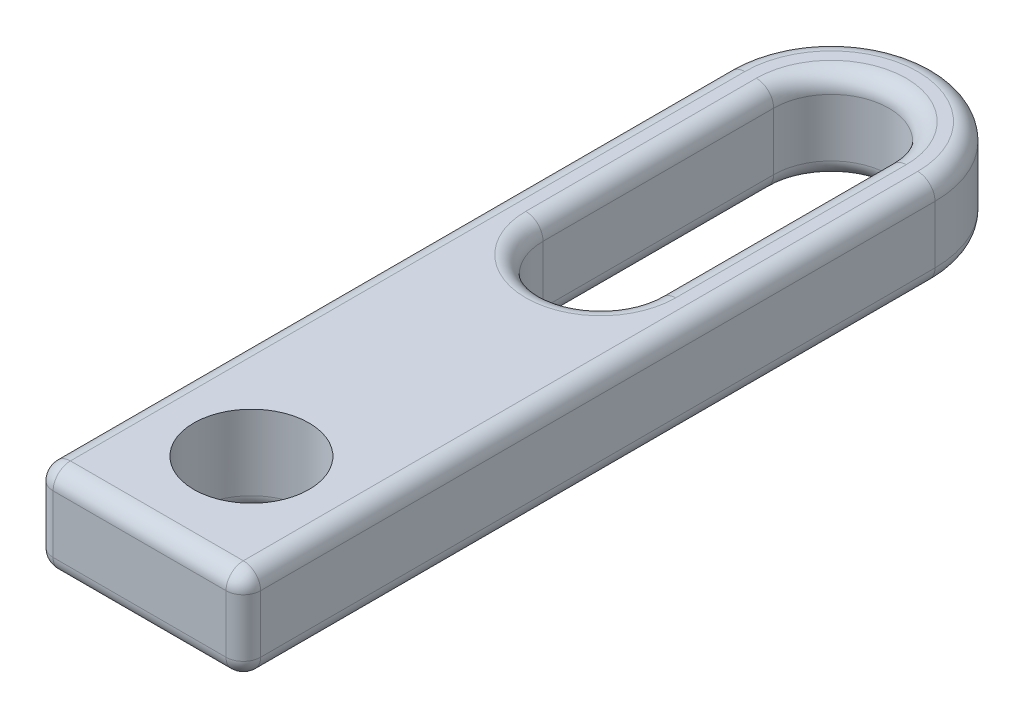
SolidWorks part; units mm, degrees
ref_plane "Front Plane" through (0, 0, 0) normal (0, 0, 1) x (1, 0, 0)
ref_plane "Top Plane" through (0, 0, 0) normal (0, 1, 0) x (1, 0, 0)
ref_plane "Right Plane" through (0, 0, 0) normal (1, 0, 0) x (0, 0, -1)
sketch "Sketch1" plane through (0, 0, 0) normal (0, 1, 0) x (1, 0, 0)
  line L0 (0, -7.5) -> (0, -17.5) construction
  line L3 (-4.5, -17.5) -> (-4.5, -7.5)
  line L4 (4.5, -32.5) -> (4.5, -7.5)
  line L5 (-4.5, -17.5) -> (-4.5, -37.5)
  line L6 (-4.5, -37.5) -> (4.5, -37.5)
  line L7 (4.5, -37.5) -> (4.5, -32.5)
  line L8 (2.5, -7.5) -> (2.5, -17.5)
  line L9 (-2.5, -7.5) -> (-2.5, -17.5)
  arc A4 (2.5, -7.5) -> (-2.5, -7.5) centre (0, -7.5) ccw
  circle A5 centre (0, -32.6492) radius 2.5
  arc A6 (-2.5, -17.5) -> (2.5, -17.5) centre (0, -17.5) ccw
  arc A7 (-4.5, -7.5) -> (4.5, -7.5) centre (0, -7.5) cw
  point P3 (0, -12.5)
  dimension "D5" = 15.1492
  dimension "D2" = 2.5
  dimension "D1" = 10
  dimension "D4" = 20
  dimension "D3" = 10
  dimension "D6" = 20
  dimension "D8" = 2
  dimension "D9" = 9
extrude "Boss-Extrude1" add sketch "Sketch1" along normal blind 4
fillet "Fillet1" radius 0.75 19 edges at (-4.5, 4, 22.5) (-4.5, 2, 37.5) (0, 4, 37.5) (2.5, 0, 12.5) (0, 0, 20) (-2.5, 0, 12.5) (0, 0, 5) (-4.5, 0, 22.5) (0, 0, 37.5) (0, 4, 3) (0, 0, 3) (4.5, 2, 37.5) (4.5, 4, 22.5) (4.5, 0, 22.5) (0, 4, 5) (2.5, 4, 12.5) (0, 4, 20) (-2.5, 4, 12.5) (0, 0, 35.1492)
